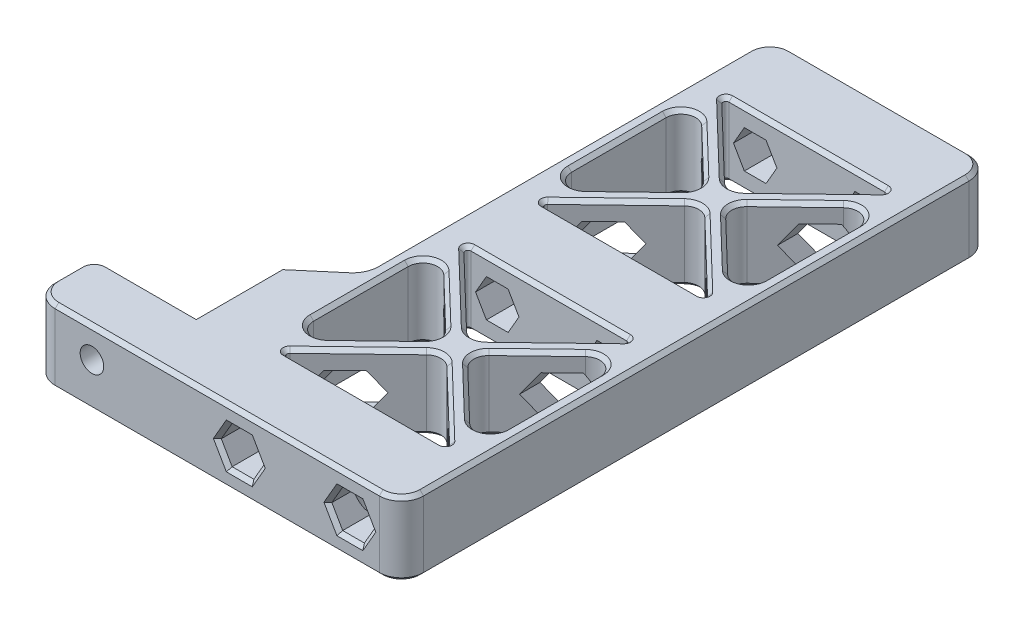
SolidWorks part; units mm, degrees
ref_plane "Front Plane" through (0, 0, 0) normal (0, 0, 1) x (1, 0, 0)
ref_plane "Top Plane" through (0, 0, 0) normal (0, 1, 0) x (1, 0, 0)
ref_plane "Right Plane" through (0, 0, 0) normal (1, 0, 0) x (0, 0, -1)
sketch "Sketch1" plane through (0, 0, 0) normal (0, 1, 0) x (1, 0, 0)
  line L1 (-31.75, -50.8) -> (31.75, -50.8)
  line L2 (-31.75, -50.8) -> (-31.75, 50.8)
  line L3 (-31.75, 50.8) -> (31.75, 50.8)
  line L4 (31.75, -50.8) -> (31.75, 50.8)
  line L5 (-31.75, -50.8) -> (31.75, 50.8) construction
  line L6 (-31.75, 50.8) -> (31.75, -50.8) construction
  point P0 (0, 0)
  dimension "D1" = 63.5
  dimension "D2" = 101.6
extrude "Boss-Extrude1" add sketch "Sketch1" along normal blind 12.7 contours L2 L3 L4 L1
sketch "Sketch2" plane through (0, 0, -50.8) normal (0, 0, -1) x (-1, 0, 0)
  line L0 (-31.75, 6.35) -> (31.75, 6.35) construction
  line L1 (-31.75, 12.7) -> (-31.75, 0) construction
  line L2 (31.75, 12.7) -> (31.75, 0) construction
  line L4 (-19.1205, 6.35) -> (-20.9903, 9.5885)
  line L5 (-20.9903, 9.5885) -> (-24.7297, 9.5885)
  line L6 (-24.7297, 9.5885) -> (-26.5995, 6.35)
  line L7 (-26.5995, 6.35) -> (-24.7297, 3.1115)
  line L8 (-24.7297, 3.1115) -> (-20.9903, 3.1115)
  line L9 (-20.9903, 3.1115) -> (-19.1205, 6.35)
  line L10 (-0.0705, 6.35) -> (-1.9403, 9.5885)
  line L11 (-1.9403, 9.5885) -> (-5.6797, 9.5885)
  line L12 (-5.6797, 9.5885) -> (-7.5495, 6.35)
  line L13 (-7.5495, 6.35) -> (-5.6797, 3.1115)
  line L14 (-5.6797, 3.1115) -> (-1.9403, 3.1115)
  line L15 (-1.9403, 3.1115) -> (-0.0705, 6.35)
  circle A0 centre (-22.86, 6.35) radius 3.2385 construction
  circle A1 centre (-3.81, 6.35) radius 3.2385 construction
  dimension "D1" = 6.35
  dimension "D2" = 6.477
  dimension "D3" = 6.477
  dimension "D4" = 19.05
  dimension "D5" = 8.89
extrude "Cut-Extrude1" cut sketch "Sketch2" against normal up to next contours L8 L9 L4 L5 L6 L7 | L14 L15 L10 L11 L12 L13
sketch "Sketch3" plane through (0, 0, 0) normal (0, -1, 0) x (1, 0, 0)
  line L0 (-31.75, 25.4) -> (31.75, 25.4) construction
  line L1 (-31.75, 50.8) -> (-31.75, -50.8) construction
  line L2 (31.75, 50.8) -> (31.75, -50.8) construction
  line L3 (-31.75, 0) -> (31.75, 0) construction
  line L4 (-31.75, 40.64) -> (-6.35, 19.05)
  line L5 (-6.35, 19.05) -> (-6.35, 0)
  line L6 (-6.35, 0) -> (-6.35, -50.8)
  line L7 (31.75, -50.8) -> (-31.75, -50.8) construction
  circle A0 centre (0, 25.4) radius 2.032
  circle A1 centre (31.75, 25.4) radius 2.032
  circle A4 centre (31.75, -25.4) radius 2.032
  circle A5 centre (0, -25.4) radius 2.032
  point P21 (-6.35, 0)
  dimension "D1" = 4.064
  dimension "D3" = 31.75
  dimension "D2" = 31.75
  dimension "D4" = 25.4
  dimension "D5" = 10.16
  dimension "D6" = 25.4
  dimension "D7" = 19.05
  dimension "D8" = 25.4
extrude "Cut-Extrude3" cut sketch "Sketch3" against normal through all and the other way through all
sketch "Sketch7" plane through (0, 0, 0) normal (0, -1, 0) x (1, 0, 0)
  line L6 (-3.81, 20.2246) -> (-3.81, 48.26)
  line L7 (-3.81, 38.1) -> (29.21, 38.1)
  line L8 (29.21, 0) -> (-3.81, 0)
  line L9 (-3.81, -38.1) -> (29.21, -38.1)
  line L11 (31.75, -50.8) -> (-31.75, -50.8) construction
  line L12 (-29.21, 41.8146) -> (-3.81, 20.2246)
  line L13 (-3.81, 20.2246) -> (-3.81, -48.26)
  line L14 (-3.81, -48.26) -> (29.21, -48.26)
  line L15 (29.21, -48.26) -> (29.21, 48.26)
  line L16 (29.21, 48.26) -> (-29.21, 48.26)
  line L17 (-29.21, 48.26) -> (-29.21, 41.8146)
  line L18 (-29.21, 41.8146) -> (-3.81, 20.2246)
  line L19 (-3.81, 20.2246) -> (-3.81, -48.26)
  line L20 (-3.81, -48.26) -> (29.21, -48.26)
  line L21 (29.21, -48.26) -> (29.21, 48.26)
  line L22 (29.21, 48.26) -> (-29.21, 48.26)
  line L23 (-29.21, 48.26) -> (-29.21, 41.8146)
  line L24 (-31.75, 50.8) -> (31.75, 50.8) construction
  line L25 (29.21, 6.35) -> (-3.81, 6.35)
  line L26 (29.21, -6.35) -> (-3.81, -6.35)
  line L27 (-3.81, 38.1) -> (29.21, 6.35) construction
  line L28 (-3.81, 6.35) -> (29.21, 38.1) construction
  line L29 (29.21, -38.1) -> (-3.81, -6.35) construction
  line L30 (29.21, -6.35) -> (-3.81, -38.1) construction
  line L31 (-4.6902, 37.1845) -> (28.3298, 5.4345)
  line L32 (-2.9298, 5.4345) -> (30.0902, 37.1845)
  line L33 (28.3298, -5.4345) -> (-4.6902, -37.1845)
  line L34 (30.0902, -37.1845) -> (-2.9298, -5.4345)
  line L35 (-2.9298, 39.0155) -> (30.0902, 7.2655)
  line L36 (-4.6902, 7.2655) -> (28.3298, 39.0155)
  line L37 (30.0902, -7.2655) -> (-2.9298, -39.0155)
  line L38 (28.3298, -39.0155) -> (-4.6902, -7.2655)
  point P43 (0, 0)
  point P53 (-15.5354, 30.1912)
  point P55 (-17.4845, 31.848)
  dimension "D2" = 12.7
  dimension "D3" = 12.7
  dimension "D6" = 1.27
  dimension "D1" = 2.54
  dimension "D4" = 6.35
  dimension "D5" = 6.35
  dimension "D7" = 1.27
extrude "Cut-Extrude6" cut sketch "Sketch7" against normal through all and the other way through all contours L19 L36 L31 L6 | L35 L36 L7 | L32 L35 L21 | L32 L25 L31 | L34 L33 L26 | L33 L38 L19 | L9 L38 L37 | L21 L37 L34
sketch "Sketch8" plane through (0, 0, 0) normal (0, -1, 0) x (1, 0, 0)
  line L0 (-27.94, 45.72) -> (-31.75, 45.72) construction
  line L2 (-27.94, 45.72) -> (-15.24, 45.72) construction
  line L3 (-31.75, 50.8) -> (-31.75, 40.64) construction
  line L4 (31.75, 44.45) -> (-7.4758, 44.45) construction
  line L5 (31.75, 50.8) -> (31.75, -50.8) construction
  line L6 (-31.75, 50.8) -> (31.75, 50.8) construction
  line L7 (31.75, 0) -> (-6.35, 0) construction
  line L8 (-6.35, 19.05) -> (-6.35, -50.8) construction
  line L9 (31.75, -44.45) -> (-6.35, -44.45) construction
  circle A0 centre (-27.94, 45.72) radius 2.032
  circle A1 centre (-15.24, 45.72) radius 2.032
  circle A2 centre (6.35, 44.45) radius 2.032
  circle A3 centre (19.05, 44.45) radius 2.032
  circle A4 centre (6.35, 0) radius 2.032
  circle A5 centre (19.05, 0) radius 2.032
  circle A6 centre (6.35, -44.45) radius 2.032
  circle A7 centre (19.05, -44.45) radius 2.032
  dimension "D1" = 5.08
  dimension "D2" = 4.064
  dimension "D6" = 12.7
  dimension "D9" = 12.7
  dimension "D3" = 12.7
  dimension "D4" = 3.81
  dimension "D5" = 6.35
  dimension "D7" = 12.7
  dimension "D8" = 6.35
  dimension "D10" = 12.7
  dimension "D11" = 12.7
  dimension "D12" = 12.7
extrude "Cut-Extrude7" cut sketch "Sketch8" against normal blind 9.525
fillet "Fillet4" radius 2.54 16 edges at (29.21, 6.35, -8.1119) (29.21, 6.35, -36.3381) (-3.81, 6.35, -36.3381) (-3.81, 6.35, -8.1119) (14.5323, 6.35, -22.225) (10.8677, 6.35, -22.225) (12.7, 6.35, -23.9869) (12.7, 6.35, -20.4631) (29.21, 6.35, 8.1119) (29.21, 6.35, 36.3381) (-3.81, 6.35, 36.3381) (-3.81, 6.35, 8.1119) (14.5323, 6.35, 22.225) (10.8677, 6.35, 22.225) (12.7, 6.35, 20.4631) (12.7, 6.35, 23.9869)
fillet "Fillet7" radius 0.508 8 edges at (27.3777, 6.35, 38.1) (-1.9777, 6.35, 38.1) (-1.9777, 6.35, 6.35) (27.3777, 6.35, 6.35) (27.3777, 6.35, -38.1) (-1.9777, 6.35, -38.1) (27.3777, 6.35, -6.35) (-1.9777, 6.35, -6.35)
fillet "Fillet1" radius 3.81 6 edges at (31.75, 6.35, -50.8) (31.75, 6.35, 50.8) (-31.75, 6.35, 50.8) (-6.35, 6.35, -50.8) (-31.75, 6.35, 40.64) (-6.35, 6.35, 19.05)
chamfer "Chamfer1" distance 0.635 angle 45 152 edges at (3.81, 3.1115, -50.8) (1.0054, 4.7308, -50.8) (1.0054, 7.9692, -50.8) (3.81, 9.5885, -50.8) (6.6146, 7.9692, -50.8) (6.6146, 4.7308, -50.8) (22.86, 3.1115, -50.8) (20.0554, 4.7307, -50.8) (20.0554, 7.9693, -50.8) (22.86, 9.5885, -50.8) (25.6646, 7.9693, -50.8) (25.6646, 4.7307, -50.8) (3.81, 9.5885, 50.8) (1.0054, 7.9692, 50.8) (1.0054, 4.7308, 50.8) (3.81, 3.1115, 50.8) (6.6146, 4.7308, 50.8) (6.6146, 7.9692, 50.8) (22.86, 9.5885, 50.8) (20.0554, 7.9693, 50.8) (20.0554, 4.7307, 50.8) (22.86, 3.1115, 50.8) (25.6646, 4.7307, 50.8) (25.6646, 7.9693, 50.8) (12.7, 0, -50.8) (0, 0, 50.8) (12.7, 12.7, -50.8) (31.75, 12.7, 0) (0, 12.7, 50.8) (-19.05, 0, 29.845) (-19.05, 12.7, 29.845) (-30.6341, 0, 49.6841) (30.6341, 0, 49.6841) (30.6341, 0, -49.6841) (-31.75, 0, 44.6959) (-31.75, 12.7, 44.6959) (30.6341, 12.7, -49.6841) (30.6341, 12.7, 49.6841) (-30.6341, 12.7, 49.6841) (-6.35, 12.7, -14.8509) (-6.35, 0, -14.8509) (-5.2341, 12.7, -49.6841) (-5.2341, 0, -49.6841) (-6.7019, 12.7, 18.8873) (-31.3981, 12.7, 40.8027) (-6.7019, 0, 18.8873) (-31.3981, 0, 40.8027) (31.75, 0, 0) (9.743, 12.7, -22.225) (4.727, 12.7, -28.1295) (-2.265, 12.7, -32.7092) (-3.81, 12.7, -22.225) (-2.265, 12.7, -11.7408) (4.727, 12.7, -16.3205) (15.657, 12.7, 22.225) (20.673, 12.7, 28.1295) (27.665, 12.7, 32.7092) (29.21, 12.7, 22.225) (27.665, 12.7, 11.7408) (20.673, 12.7, 16.3205) (12.7, 12.7, -19.4794) (4.9355, 12.7, -12.9973) (-1.1876, 12.7, -6.6682) (12.7, 12.7, -6.35) (26.5876, 12.7, -6.6682) (20.4645, 12.7, -12.9973) (26.5876, 12.7, 6.6682) (12.7, 12.7, 6.35) (-1.1876, 12.7, 6.6682) (4.9355, 12.7, 12.9973) (12.7, 12.7, 19.4794) (20.4645, 12.7, 12.9973) (9.743, 12.7, 22.225) (4.727, 12.7, 16.3205) (-2.265, 12.7, 11.7408) (-3.81, 12.7, 22.225) (-2.265, 12.7, 32.7092) (4.727, 12.7, 28.1295) (26.5876, 12.7, 37.7818) (20.4645, 12.7, 31.4527) (12.7, 12.7, 24.9706) (4.9355, 12.7, 31.4527) (-1.1876, 12.7, 37.7818) (12.7, 12.7, 38.1) (15.657, 12.7, -22.225) (20.673, 12.7, -16.3205) (27.665, 12.7, -11.7408) (29.21, 12.7, -22.225) (27.665, 12.7, -32.7092) (20.673, 12.7, -28.1295) (12.7, 12.7, -24.9706) (20.4645, 12.7, -31.4527) (26.5876, 12.7, -37.7818) (12.7, 12.7, -38.1) (-1.1876, 12.7, -37.7818) (4.9355, 12.7, -31.4527) (26.5876, 0, -37.7818) (20.4645, 0, -31.4527) (12.7, 0, -24.9706) (4.9355, 0, -31.4527) (-1.1876, 0, -37.7818) (12.7, 0, -38.1) (-2.265, 0, 11.7408) (4.727, 0, 16.3205) (9.743, 0, 22.225) (4.727, 0, 28.1295) (-2.265, 0, 32.7092) (-3.81, 0, 22.225) (12.7, 0, 19.4794) (4.9355, 0, 12.9973) (-1.1876, 0, 6.6682) (12.7, 0, 6.35) (26.5876, 0, 6.6682) (20.4645, 0, 12.9973) (-1.1876, 0, -6.6682) (4.9355, 0, -12.9973) (12.7, 0, -19.4794) (20.4645, 0, -12.9973) (26.5876, 0, -6.6682) (12.7, 0, -6.35) (27.665, 0, 11.7408) (29.21, 0, 22.225) (27.665, 0, 32.7092) (20.673, 0, 28.1295) (15.657, 0, 22.225) (20.673, 0, 16.3205) (-2.265, 0, -11.7408) (-3.81, 0, -22.225) (-2.265, 0, -32.7092) (4.727, 0, -28.1295) (9.743, 0, -22.225) (4.727, 0, -16.3205) (12.7, 0, 24.9706) (20.4645, 0, 31.4527) (26.5876, 0, 37.7818) (12.7, 0, 38.1) (-1.1876, 0, 37.7818) (4.9355, 0, 31.4527) (27.665, 0, -11.7408) (20.673, 0, -16.3205) (15.657, 0, -22.225) (20.673, 0, -28.1295) (27.665, 0, -32.7092) (29.21, 0, -22.225) (6.35, 0, -2.032) (19.05, 0, 42.418) (6.35, 0, 42.418) (-15.24, 0, 43.688) (19.05, 0, -46.482) (6.35, 0, -46.482) (19.05, 0, -2.032) (-27.94, 0, 43.688)
sketch "Sketch5" plane through (0, 0, 50.8) normal (0, 0, 1) x (1, 0, 0)
  line L0 (-21.6491, 3.1754) -> (-31.75, 3.1754)
  line L1 (-17.7405, 5.3975) -> (-13.5244, 12.7)
  line L2 (-24.9906, 20.7631) -> (-26.0206, 7.9769)
  line L3 (-17.1514, 7.859) -> (-17.8412, 20.668)
  line L4 (-24.9906, 20.7631) -> (-26.0206, 7.9769)
  line L5 (-17.1514, 7.859) -> (-17.8412, 20.668)
  line L6 (-27.94, 0.635) -> (-27.94, 12.065) construction
  line L7 (-27.94, 12.065) -> (-31.75, 12.065) construction
  line L8 (-31.75, 12.065) -> (-31.75, 0.635) construction
  line L9 (-31.75, 0.635) -> (-27.94, 0.635) construction
  line L10 (27.94, 12.065) -> (27.94, 12.7) construction
  line L11 (27.94, 12.7) -> (-27.94, 12.7) construction
  line L12 (-27.94, 12.7) -> (-27.94, 12.065) construction
  line L13 (-27.94, 12.065) -> (27.94, 12.065) construction
  line L14 (-27.94, 0.635) -> (-27.94, 12.065)
  line L15 (-27.94, 12.065) -> (-31.75, 12.065)
  line L16 (-31.75, 12.065) -> (-31.75, 0.635)
  line L17 (-31.75, 0.635) -> (-27.94, 0.635)
  line L18 (27.94, 12.065) -> (27.94, 12.7)
  line L19 (27.94, 12.7) -> (-27.94, 12.7)
  line L20 (-27.94, 12.7) -> (-27.94, 12.065)
  line L21 (-27.94, 12.065) -> (27.94, 12.065)
  circle A1 centre (-21.59, 7.62) radius 2.032
  circle A2 centre (-21.59, 7.62) radius 2.032
  circle A3 centre (-20.9146, 58.4155) radius 2.032
  circle A4 centre (-20.9146, 58.4155) radius 2.032
  arc A10 (-17.933, 22.5616) -> (-17.8412, 20.668) centre (159.7016, 30.2285) ccw
  arc A11 (-12.3265, 56.1183) -> (-17.933, 22.5616) centre (159.435, 10.1746) ccw
  arc A12 (-12.3265, 56.1183) -> (-29.5607, 56.3475) centre (-20.9146, 58.4155) ccw
  arc A13 (-24.8484, 22.6536) -> (-29.5607, 56.3475) centre (-202.483, 14.9867) ccw
  arc A14 (-24.9906, 20.7631) -> (-24.8484, 22.6536) centre (-202.2164, 35.0405) ccw
  arc A15 (-26.0206, 7.9769) -> (-17.1514, 7.859) centre (-21.59, 7.62) ccw
  arc A16 (-17.933, 22.5616) -> (-17.8412, 20.668) centre (159.7016, 30.2285) ccw
  arc A17 (-12.3265, 56.1183) -> (-17.933, 22.5616) centre (159.435, 10.1746) ccw
  arc A18 (-12.3265, 56.1183) -> (-29.5607, 56.3475) centre (-20.9146, 58.4155) ccw
  arc A19 (-24.8484, 22.6536) -> (-29.5607, 56.3475) centre (-202.483, 14.9867) ccw
  arc A20 (-24.9906, 20.7631) -> (-24.8484, 22.6536) centre (-202.2164, 35.0405) ccw
  arc A21 (-26.0206, 7.9769) -> (-17.1514, 7.859) centre (-21.59, 7.62) ccw
  dimension "D4" = 60
  dimension "D1" = 0
  dimension "D2" = 0
  dimension "D3" = 0
extrude "Cut-Extrude4" cut sketch "Sketch5" against normal up to next contours A2
ref_plane "Plane1" through (0, 0, 40.259) normal (0, 0, 1) x (1, 0, 0)
sketch "Sketch6" plane through (0, 0, 40.259) normal (0, 0, 1) x (1, 0, 0)
  line L0 (-17.7405, 5.3975) -> (-13.5244, 12.7) construction
  line L1 (-21.6491, 3.1754) -> (-31.75, 3.1754) construction
  line L2 (-17.7405, 5.3975) -> (-13.5244, 12.7)
  line L3 (-21.6491, 3.1754) -> (-31.75, 3.1754)
  line L4 (-13.5244, 12.7) -> (-31.75, 12.7)
  line L5 (-31.75, 12.7) -> (-31.75, 3.1754)
  circle A0 centre (-21.59, 7.62) radius 2.032 construction
  arc A1 (-26.0206, 7.9769) -> (-17.1514, 7.859) centre (-21.59, 7.62) ccw construction
  circle A2 centre (-21.59, 7.62) radius 2.032
  arc A3 (-26.0206, 7.9769) -> (-17.1514, 7.859) centre (-21.59, 7.62) ccw
extrude "Cut-Extrude5" cut sketch "Sketch6" against normal through all
fillet "Fillet3" radius 2.54 1 edges at (-31.0903, 7.6202, 40.259)
chamfer "Chamfer3" distance 0.635 angle 45 2 edges at (-29.9382, 12.7, 40.3656) (-21.3672, 12.7, 40.259)
